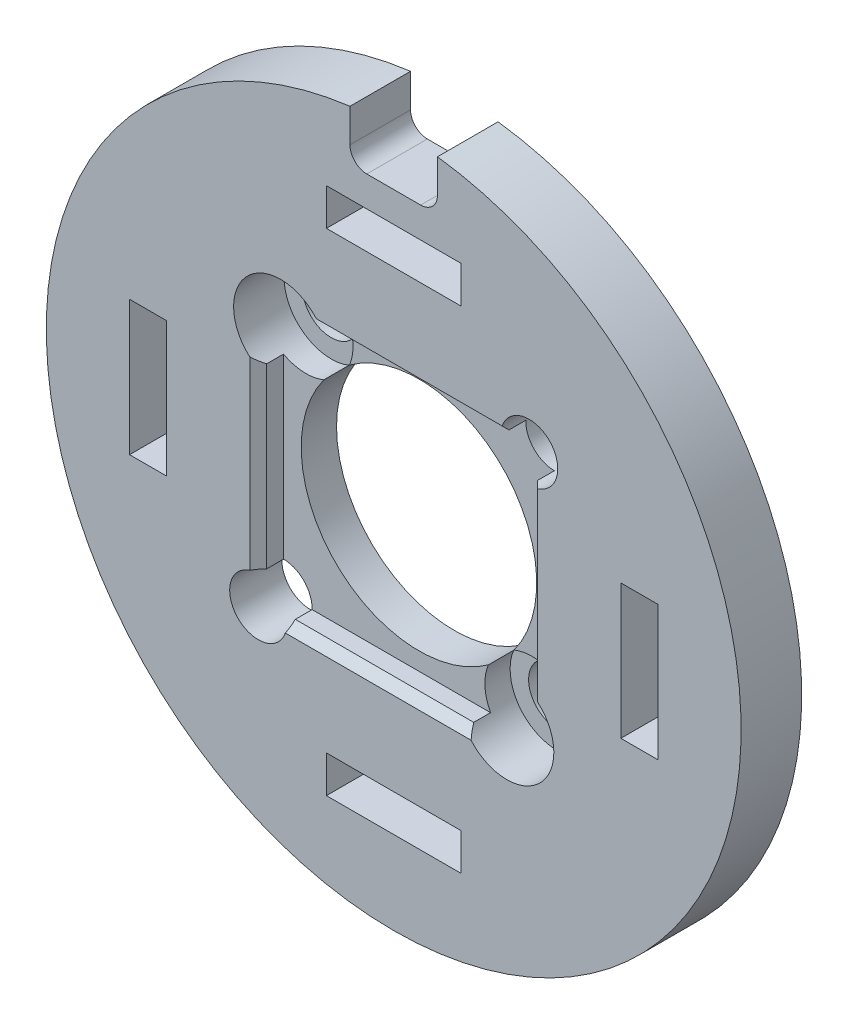
SolidWorks part; units mm, degrees
other "标注1"
sketch "草图10" plane through (17.4, 17.4, 7.6) normal (0.4476, 0.4282, 0.7851) x (0.8625, 0.025, -0.5054)
ref_plane "前视基准面" through (0, 0, 0) normal (0, 0, 1) x (1, 0, 0)
ref_plane "上视基准面" through (0, 0, 0) normal (0, 1, 0) x (1, 0, 0)
ref_plane "右视基准面" through (0, 0, 0) normal (1, 0, 0) x (0, 0, -1)
other "Configuration Table"
sketch "草图1" plane through (0, 0, 0) normal (0, 0, 1) x (1, 0, 0)
  circle A0 centre (0, 0) radius 17.4
  dimension "D1" = 34.8
extrude "凸台-拉伸1" add sketch "草图1" along normal blind 5.6
sketch "草图2" plane through (0, 0, 5.6) normal (0, 0, 1) x (1, 0, 0)
  line L0 (5.5154, -5.5154) -> (6.7175, -6.7175) construction
  line L1 (-6.7175, 6.7175) -> (-5.0175, 6.7175)
  line L2 (-6.7175, 6.7175) -> (-6.7175, 5.0175)
  line L3 (5.0175, -6.7175) -> (6.7175, -6.7175)
  line L4 (6.7175, -5.0175) -> (6.7175, -6.7175)
  line L5 (-6.7175, 6.7175) -> (-0.0325, 0.0325) construction
  line L6 (-6.7175, 6.7175) -> (6.7175, -6.7175)
  circle A0 centre (-6.7175, 6.7175) radius 1.7
  circle A2 centre (6.7175, -6.7175) radius 1.7
  arc A4 (-5.5154, -5.5154) -> (-6.7175, -5.0175) centre (-6.7175, -6.7175) ccw [skipped]
  arc A5 (5.0175, 6.7175) -> (5.5154, 5.5154) centre (6.7175, 6.7175) ccw [skipped]
  point P0 (0, 0)
  point P16 (0, 0)
  dimension "D3" = 3.4
  dimension "D1" = 19
  dimension "D2" = 9.5
  dimension "D4" = 4
extrude "切除-拉伸1" cut sketch "草图2" against normal through all contours A0 | A2
sketch "草图3" plane through (0, 0, 5.6) normal (0, 0, 1) x (1, 0, 0)
  circle A0 centre (0, 0) radius 7
  dimension "D1" = 14
extrude "切除-拉伸2" cut sketch "草图3" against normal through all
sketch "草图4" plane through (0, 0, 5.6) normal (0, 0, 1) x (1, 0, 0)
  circle A1 centre (-6.7175, 6.7175) radius 2.8
  circle A2 centre (6.7175, -6.7175) radius 2.8
  dimension "D1" = 5.6
  dimension "D2" = 5.6
extrude "切除-拉伸3" cut sketch "草图4" against normal blind 3
sketch "草图5" plane through (0, 0, 5.6) normal (0, 0, 1) x (1, 0, 0)
  line L1 (-8.05, 8) -> (8.05, 8)
  line L2 (-8.05, 8) -> (-8.05, -8)
  line L3 (-8.05, -8) -> (8.05, -8)
  line L4 (8.05, 8) -> (8.05, -8)
  line L5 (-8.05, 8) -> (8.05, -8) construction
  line L6 (-8.05, -8) -> (8.05, 8) construction
  circle A0 centre (8.05, 8) radius 1.7
  circle A1 centre (-8.05, -8) radius 1.7
  point P0 (0, 0)
  dimension "D3" = 3.4
  dimension "D4" = 3.4
  dimension "D1" = 16.1
  dimension "D2" = 16
extrude "切除-拉伸4" cut sketch "草图5" against normal through all contours A1 | A0
sketch "草图6" plane through (0, 0, 0) normal (0, 0, -1) x (-1, 0, 0)
  line L0 (4.7668, -8) -> (6.4084, -10.8433)
  line L1 (-4.7668, 8) -> (-6.4084, 10.8433)
  line L2 (-6.4084, 10.8433) -> (-9.6916, 10.8433)
  line L3 (-9.6916, 10.8433) -> (-11.3332, 8)
  line L4 (-11.3332, 8) -> (-9.6916, 5.1567)
  line L5 (-9.6916, 5.1567) -> (-6.4084, 5.1567)
  line L6 (-6.4084, 5.1567) -> (-4.7668, 8)
  line L7 (6.4084, -10.8433) -> (9.6916, -10.8433)
  line L8 (9.6916, -10.8433) -> (11.3332, -8)
  line L9 (11.3332, -8) -> (9.6916, -5.1567)
  line L10 (9.6916, -5.1567) -> (6.4084, -5.1567)
  line L11 (6.4084, -5.1567) -> (4.7668, -8)
  circle A0 centre (-8.05, 8) radius 2.8433 construction
  point P17 (0, 0)
  dimension "D1" = 2
extrude "切除-拉伸5" cut sketch "草图6" against normal blind 2.5
sketch "草图7" plane through (0, 0, 5.6) normal (0, 0, 1) x (1, 0, 0)
  line L5 (-8.05, 8.05) -> (8.05, 8.05)
  line L6 (-8.05, 8.05) -> (-8.05, -8.05)
  line L11 (-8.05, -8.05) -> (8.05, -8.05)
  line L12 (8.05, 8.05) -> (8.05, -8.05)
  line L13 (-8.05, 8.05) -> (8.05, -8.05) construction
  line L14 (-8.05, -8.05) -> (8.05, 8.05) construction
  point P0 (0, 0)
  dimension "D1" = 16.1
  dimension "D2" = 16.1
extrude "切除-拉伸6" cut sketch "草图7" against normal blind 1.5
chamfer "倒角1" distance 0.5 angle 45 4 edges at (1.0479, 8.05, 5.6) (8.05, 1.0226, 5.6) (-1.0479, -8.05, 5.6) (-8.05, -1.0226, 5.6)
sketch "草图8" plane through (0, 0, 0) normal (1, 0, 0) x (0, 0, -1)
  line L0 (0, 17.4) -> (0, 17.2)
  line L1 (0, 17.4) -> (0.2, 17.4)
  line L2 (0.2, 17.4) -> (0, 17.2)
  dimension "D1" = 0.2
  dimension "D2" = 0.2
ref_axis "基准轴1" through (0, 0, 0) along (0, 0, 1)
revolve "旋转1" add sketch "草图8" angle 360 about axis through (0, 0, 0) along (0, 0, 1)
sketch "草图9" plane through (0, 0, 5.6) normal (0, 0, 1) x (1, 0, 0)
  line L0 (0, 0) -> (15, 0) construction
  line L1 (4, -13.5) -> (-4, -13.5)
  line L2 (13.5, 4) -> (16.5, 4)
  line L3 (13.5, 4) -> (13.5, -4)
  line L4 (13.5, -4) -> (16.5, -4)
  line L5 (16.5, 4) -> (16.5, -4)
  line L6 (13.5, 4) -> (16.5, -4) construction
  line L7 (13.5, -4) -> (16.5, 4) construction
  line L8 (4, -13.5) -> (4, -16.5)
  line L9 (4, -16.5) -> (-4, -16.5)
  line L10 (-4, -13.5) -> (-4, -16.5)
  line L11 (-13.5, -4) -> (-13.5, 4)
  line L12 (-13.5, -4) -> (-16.5, -4)
  line L13 (-16.5, -4) -> (-16.5, 4)
  line L14 (-13.5, 4) -> (-16.5, 4)
  line L15 (-4, 13.5) -> (4, 13.5)
  line L16 (-4, 13.5) -> (-4, 16.5)
  line L17 (-4, 16.5) -> (4, 16.5)
  line L18 (4, 13.5) -> (4, 16.5)
  line L19 (15.7, 4) -> (15.7, -4)
  line L20 (4, -15.7) -> (-4, -15.7)
  line L21 (-15.7, -4) -> (-15.7, 4)
  line L22 (-4, 15.7) -> (4, 15.7)
  point P22 (0, 0)
  point P31 (0, 0)
  dimension "D1" = 15
  dimension "D2" = 3
  dimension "D3" = 8
  dimension "D5" = 0.8
  dimension "D4" = 4
  dimension "D6" = 4
extrude "切除-拉伸7" cut sketch "草图9" against normal through all contours L19 L2 L3 L4 | L22 L16 L15 L18 | L21 L12 L11 L14 | L20 L8 L1 L10 region at (0, -14.6, 5.6) region at (14.6, 0, 5.6) region at (-14.6, 0, 5.6) region at (0, 14.6, 5.6)
sketch "Sketch1" plane through (0, 0, 0) normal (0, 0, 1) x (1, 0, 0)
  circle A0 centre (0, 0) radius 17.4
  circle A1 centre (0, 0) radius 20.65
  dimension "D1" = 41.3
extrude "Boss-Extrude1" add sketch "Sketch1" along normal up to surface (5.6 mm away) and the other way blind 4 up to face at (0, 0, 5.6)
sketch "Sketch2" plane through (0, 0, -4) normal (0, 0, -1) x (-1, 0, 0)
  line L0 (0, 0) -> (-17.5, 0)
  line L1 (-17.5, 0) -> (-17.5, 4)
  line L2 (-17.5, 4) -> (-20, 4)
  line L3 (-20, 4) -> (-20, -4)
  line L4 (-20, -4) -> (-17.5, -4)
  line L5 (-17.5, -4) -> (-17.5, 0)
  dimension "D1" = 2.5
  dimension "D2" = 4
  dimension "D3" = 4
  dimension "D4" = 17.5
sketch "Sketch3" plane through (0, 0, -4) normal (0, 0, -1) x (-1, 0, 0)
  circle A0 centre (0, 0) radius 20.65
  circle A1 centre (0, 0) radius 23
  circle M10 centre (0, 0) radius 20.65
  dimension "D1" = 46
extrude "Boss-Extrude2" add sketch "Sketch3" against normal blind 2.5 contours A1 M10 region at (22.3495, 0, -4)
sketch "Sketch4" plane through (0, 0, -4) normal (0, 0, -1) x (-1, 0, 0)
  circle A0 centre (0, 0) radius 18
  dimension "D1" = 36
extrude "Cut-Extrude3" cut sketch "Sketch4" against normal up to surface (4 mm away) up to face at (0, 14.6, 0)
sketch "Sketch5" plane through (0, 0, -4) normal (0, 0, -1) x (-1, 0, 0)
  line L13 (0, 0) -> (23, 0)
  line L14 (0, 0) -> (-23, 0)
  line L15 (23, -4) -> (22, -4)
  line L16 (23, -4) -> (23, 4)
  line L17 (23, 4) -> (22, 4)
  line L18 (22, -4) -> (22, 4)
  line L19 (-23, 4) -> (-22, 4)
  line L20 (-23, 4) -> (-23, -4)
  line L21 (-23, -4) -> (-22, -4)
  line L22 (-22, 4) -> (-22, -4)
  circle A0 centre (0, 0) radius 23 construction
  point P9 (0, 22)
  point P19 (0, -22)
  point P23 (0, 0)
  point P34 (0, 0)
  dimension "D4" = 8
  dimension "D5" = 1
  dimension "D6" = 4
  dimension "D3" = 2
  dimension "D7" = 2
extrude "Cut-Extrude4" cut sketch "Sketch5" against normal blind 10 contours L19 L22 L21 L20 | L16 L15 L18 L17
sketch "Sketch7" plane through (0, 0, -4) normal (0, 0, -1) x (-1, 0, 0)
  line L1 (0, 22.3) -> (2.6, 22.3)
  line L2 (0, 17.5) -> (-2.6, 17.5)
  line L3 (0, 17.5) -> (0, 22.3)
  line L4 (0, 22.3) -> (-2.6, 22.3)
  line L5 (-2.6, 17.5) -> (-2.6, 22.3)
  line L7 (0, 22.3) -> (0, 17.5)
  line L10 (0, 22.3) -> (0, 17.5)
  line L11 (0, 17.5) -> (2.6, 17.5)
  line L12 (2.6, 22.3) -> (2.6, 17.5)
  circle M5 centre (0, 0) radius 18
  dimension "D1" = 2.6
  dimension "D2" = 2.6
  dimension "D3" = 4.8
extrude "Cut-Extrude6" cut sketch "Sketch7" against normal blind 10 contours L5 L3 L4 M5 | L5 L2 L3 M5 | L12 L1 L3 M5 | L12 L3 L11 M5 region at (-1.3094, 20.1182, -4) region at (1.3094, 20.1182, -4) region at (-1.2066, 17.7222, -4) region at (1.2066, 17.7222, -4)
fillet "Fillet3" radius 1 4 edges at (2.6, 22.3, -2.75) (-2.6, 22.3, -2.75) (-2.6, 17.5, 2.8) (2.6, 17.5, 2.8)
sketch "Sketch8" plane through (0, 0, 5.6) normal (0, 0, 1) x (1, 0, 0)
  circle A0 centre (0, 0) radius 23
sketch "Sketch9" plane through (0, 0, -4) normal (0, 0, -1) x (-1, 0, 0)
  circle A0 centre (0, 0) radius 23
extrude "Cut-Extrude7" cut sketch "Sketch9" against normal blind 6
